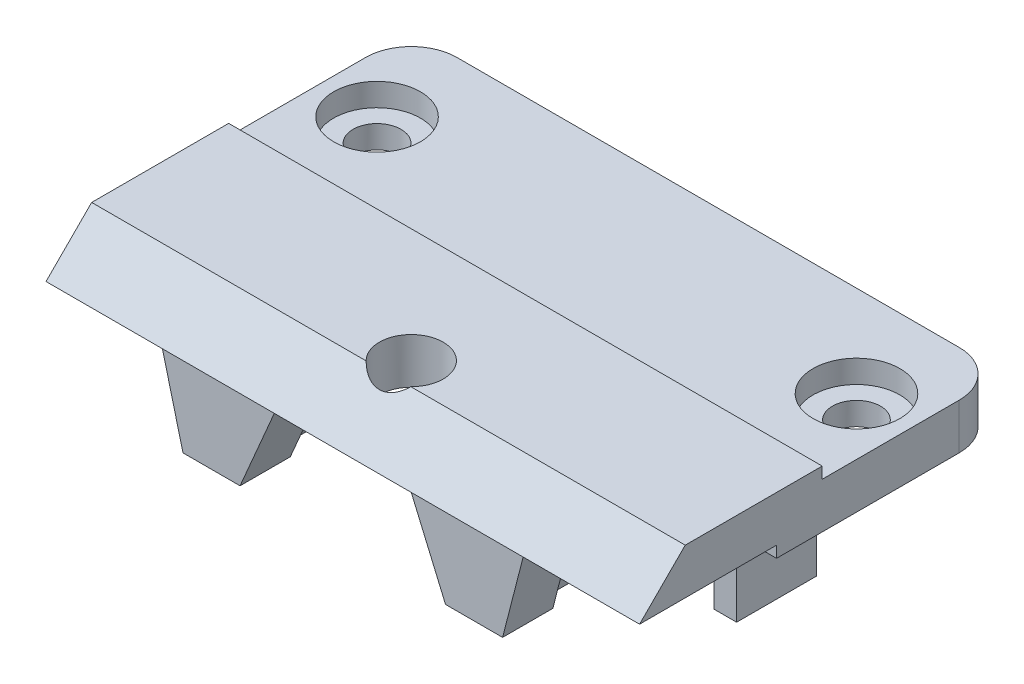
SolidWorks part; units mm, degrees
material "ABS"
ref_plane "正面" through (0, 0, 0) normal (0, 0, 1) x (1, 0, 0)
ref_plane "平面" through (0, 0, 0) normal (0, 1, 0) x (1, 0, 0)
ref_plane "右側面" through (0, 0, 0) normal (1, 0, 0) x (0, 0, -1)
sketch "ｽｹｯﾁ1" plane through (0, 0, 0) normal (0, 1, 0) x (1, 0, 0)
  line L0 (-13, 8) -> (13, 8)
  line L2 (-13, 8) -> (-13, -8)
  line L3 (-13, -8) -> (13, -8)
  line L4 (13, 8) -> (13, -8)
  line L5 (-13, 8) -> (13, -8) construction
  line L6 (-13, -8) -> (13, 8) construction
  point P7 (0, 0)
  dimension "D1" = 0
  dimension "D2" = 0
  dimension "D4" = 16
  dimension "D3" = 26
extrude "ﾎﾞｽ - 押し出し1" add sketch "ｽｹｯﾁ1" along normal blind 2
sketch "ｽｹｯﾁ4" plane through (0, 0, 8) normal (0, 0, 1) x (1, 0, 0)
  line L1 (-7, -3.5) -> (-4.5, -3.5)
  line L2 (-4.5, -3.5) -> (-3, 0)
  line L4 (3, 0) -> (4.5, -3.5)
  line L5 (4.5, -3.5) -> (7, -3.5)
  line L8 (7, -3.5) -> (7.9, 0)
  line L10 (-7, -3.5) -> (-7.9, 0)
  line L12 (3, 0) -> (0, 0) construction
  line L13 (0, 0) -> (-3, 0) construction
  line L14 (-7.9, 0) -> (-3, 0)
  line L15 (3, 0) -> (7.9, 0)
  line L16 (-13, 0) -> (13, 0) construction
  dimension "D1" = 3
  dimension "D2" = 0
  dimension "D3" = 7
  dimension "D4" = 7.9
  dimension "D5" = 2.5
  dimension "D9" = 3.5
extrude "ﾎﾞｽ - 押し出し3" add sketch "ｽｹｯﾁ4" against normal blind 6
sketch "ｽｹｯﾁ5" plane through (0, 2, 0) normal (0, 1, 0) x (1, 0, 0)
  line L1 (-13, -8) -> (13, -8) construction
  circle A0 centre (0, -5) radius 1.4
  dimension "D1" = 2.8
  dimension "D2" = 1.4
  dimension "D3" = 3
  dimension "D4" = 0
extrude "ｶｯﾄ - 押し出し1" cut sketch "ｽｹｯﾁ5" against normal up to next
fillet "ﾌｨﾚｯﾄ1" [suppressed] radius 2
sketch "ｽｹｯﾁ6" plane through (13, 0, 0) normal (1, 0, 0) x (0, 0, -1)
  line L0 (8, 2) -> (8, 0) construction
  line L1 (-2, 0) -> (8, 0)
  line L2 (-2, 0) -> (-2, -0.5)
  line L3 (-2, -0.5) -> (8, -0.5)
  line L4 (8, 0) -> (8, -0.5)
  line L5 (-2, 0) -> (8, -0.5) construction
  line L6 (-2, -0.5) -> (8, 0) construction
  point P4 (3, -0.25)
  dimension "D1" = 0.5
extrude "ﾎﾞｽ - 押し出し4" add sketch "ｽｹｯﾁ6" against normal up to surface (26 mm away) up to face at (-13, 1, 0)
sketch "ｽｹｯﾁ7" plane through (13, 0, 0) normal (1, 0, 0) x (0, 0, -1)
  line L0 (-8, 2) -> (8, 2) construction
  line L1 (0, 2) -> (8, 2)
  line L2 (0, 2) -> (0, 1.5)
  line L3 (0, 1.5) -> (8, 1.5)
  line L4 (8, 2) -> (8, 1.5)
  line L5 (0, 2) -> (8, 1.5) construction
  line L6 (0, 1.5) -> (8, 2) construction
  line L7 (8, 2) -> (8, -0.5) construction
  point P4 (4, 1.75)
  dimension "D1" = 0.5
  dimension "D2" = 8
extrude "ｶｯﾄ - 押し出し2" cut sketch "ｽｹｯﾁ7" against normal up to next
hole_wizard "M2 丸平ねじ用座ぐり穴1" positions "ｽｹｯﾁ8" profile "ｽｹｯﾁ9" counterbore size "M2" standard "JIS" end condition through all
sketch "ｽｹｯﾁ8" plane through (0, 1.5, 0) normal (0, 1, 0) x (1, 0, 0)
  line L0 (-13, 8) -> (13, 8) construction
  point P0 (10.5, 4)
  dimension "D1" = 4
  dimension "D2" = 10.5
sketch "ｽｹｯﾁ9" plane through (10.5, 1.5, -4) normal (1, 0, 0) x (0, 0, 1)
  line L0 (0, 0) -> (0, 5)
  line L1 (0, 5) -> (1.05, 5)
  line L3 (1.05, 5) -> (1.05, 1)
  line L4 (1.05, 1) -> (1.9, 1)
  line L5 (1.9, 1) -> (1.9, 0)
  line L7 (1.9, 0) -> (0, 0)
  line L11 (0, -6.35) -> (0, 107.95) construction
  dimension "通し穴の直径" = 2.1
  dimension "通し穴の深さ" = 5
  dimension "座ぐり穴の直径" = 3.8
  dimension "座ぐり穴の深さ" = 1
sketch "ｽｹｯﾁ10" plane through (0, -0.5, 0) normal (0, -1, 0) x (1, 0, 0)
  line L0 (7.7714, 2) -> (13, 2) construction
  line L1 (10.25, 2) -> (11.25, 2)
  line L2 (10.25, 2) -> (10.25, -1.5)
  line L3 (10.25, -1.5) -> (11.25, -1.5)
  line L4 (11.25, 2) -> (11.25, -1.5)
  line L5 (10.25, 2) -> (11.25, -1.5) construction
  line L6 (10.25, -1.5) -> (11.25, 2) construction
  line L7 (-13, -8) -> (13, -8) construction
  line L8 (13, 2) -> (13, -8) construction
  point P4 (10.75, 0.25)
  dimension "D1" = 6.5
  dimension "D2" = 1.75
  dimension "D3" = 1
extrude "ﾎﾞｽ - 押し出し5" add sketch "ｽｹｯﾁ10" along normal blind 3.3
mirror "ﾐﾗｰ1" about plane through (0, 0, 0) normal (1, 0, 0) of "M2 丸平ねじ用座ぐり穴1", "ﾎﾞｽ - 押し出し5"
chamfer "面取り1" distance 2 angle 45 1 edges at (0, 2, 8)
fillet "ﾌｨﾚｯﾄ2" radius 2 2 edges at (-13, 0.5, -8) (13, 0.5, -8)
sketch "ｽｹｯﾁ11" plane through (0, -0.5, 0) normal (0, -1, 0) x (1, 0, 0)
  line L0 (-10.5, -4) -> (-10.5, -1.5)
  line L1 (-10.25, -1.5) -> (-11.25, -1.5) construction
  line L2 (-10.5, -4) -> (-10.5, -8)
  line L3 (-11, -8) -> (11, -8) construction
ref_plane "平面1" through (0, 0, 5) normal (0, 0, 1) x (1, 0, 0)
sketch "ｽｹｯﾁ12" plane through (0, 0, 5) normal (0, 0, 1) x (1, 0, 0)
  line L0 (-7.9, 0) -> (-7, -3.5)
  line L1 (-7, -3.5) -> (-4.5, -3.5) construction
  line L2 (-7.9, 0) -> (-7, -3.5) construction
  line L3 (-7, -3.5) -> (-6.4, -3.5)
  line L4 (-6.4, -3.5) -> (-7.3, 0)
  line L5 (-7.3, 0) -> (-7.9, 0)
  line L6 (-3, 0) -> (-4.5, -3.5)
  line L7 (-4.5, -3.5) -> (-5.1, -3.5)
  line L8 (-5.1, -3.5) -> (-3.6, 0)
  line L9 (-3, 0) -> (-7.9, 0) construction
  line L10 (-3.6, 0) -> (-3, 0)
  dimension "D1" = 0.6
  dimension "D2" = 0.6
extrude "ｶｯﾄ - 押し出し3" cut sketch "ｽｹｯﾁ12" against normal mid plane 1.6
mirror "ﾐﾗｰ2" about plane through (0, 0, 0) normal (1, 0, 0) of "ｶｯﾄ - 押し出し3"
